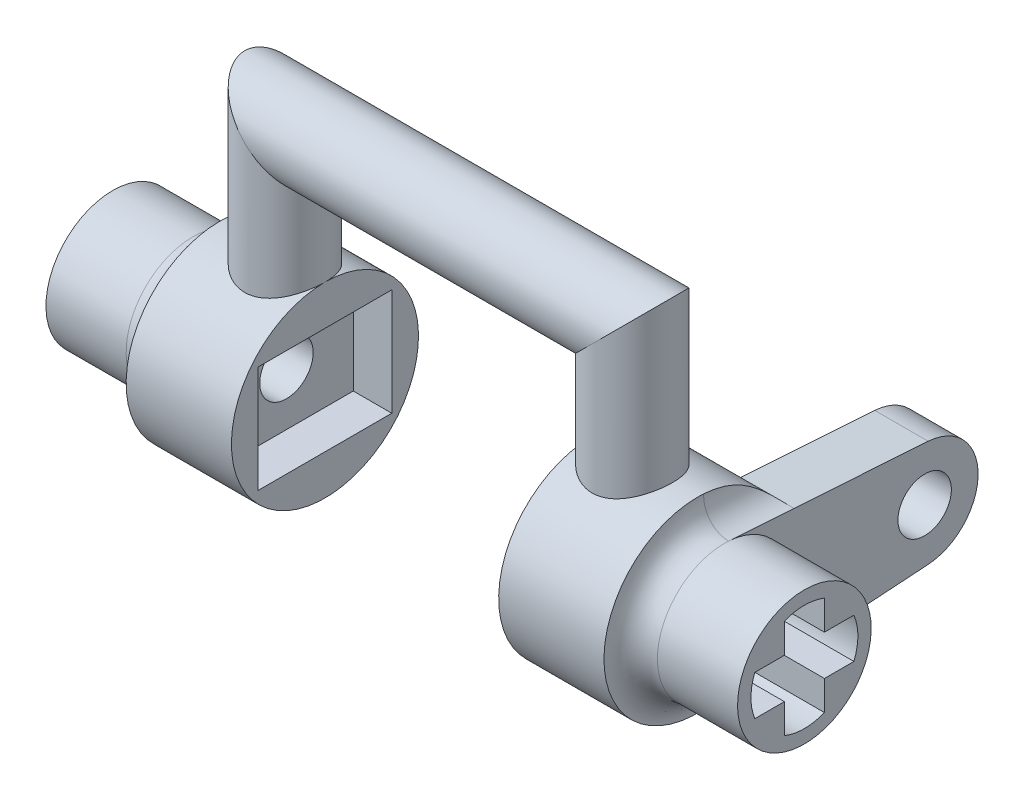
SolidWorks part; units mm, degrees
ref_plane "前视基准面" through (0, 0, 0) normal (0, 0, 1) x (1, 0, 0)
ref_plane "上视基准面" through (0, 0, 0) normal (0, 1, 0) x (1, 0, 0)
ref_plane "右视基准面" through (0, 0, 0) normal (1, 0, 0) x (0, 0, -1)
other "Configuration Table"
sketch "草图1" plane through (0, 0, 0) normal (0, 0, 1) x (1, 0, 0)
  line L0 (-210.8221, 0) -> (10330.2839, 0) construction
  line L1 (0, 0) -> (0, 8) construction
  line L2 (-6.5, 8) -> (6.5, 8)
  line L3 (6.5, 8) -> (6.5, 0)
  line L4 (6.5, 0) -> (9.5, 0)
  line L5 (-6.5, 8) -> (-6.5, 0)
  line L6 (-6.5, 0) -> (-9.5, 0)
  point P8 (0, 8)
  dimension "D1" = 8
  dimension "D2" = 13
  dimension "D3" = 3
  dimension "D4" = 3
sweep "扫描1" add path "草图1" circular profile diameter 3 parameters "D3"=3
sketch "草图8" plane through (0, 0, 0) normal (1, 0, 0) x (0, 0, -1)
  circle A0 centre (0, 0) radius 2.5
  dimension "D1" = 5
extrude "凸台-拉伸1" add sketch "草图8" along normal blind 3.44 and the other way blind 4.5 from surface starting at face at (9.5, 1.5, 0)
sketch "草图9" plane through (0, 0, 0) normal (1, 0, 0) x (0, 0, -1)
  circle A1 centre (0, 0) radius 2.5
  circle A2 centre (0, 0) radius 2.5
  dimension "D1" = 0
extrude "凸台-拉伸2" add sketch "草图9" against normal blind 3.44 and the other way blind 4.5 from surface starting at face at (-9.5, 1.5, 0)
ref_plane "基准面1" through (9.94, 0, 0) normal (1, 0, 0) x (0, 0, -1)
sketch "草图10" plane through (0, 0, 0) normal (1, 0, 0) x (0, 0, -1)
  line L0 (0.75, 0.75) -> (1.854, 0.75)
  line L1 (-1.854, 0.75) -> (-0.75, 0.75)
  line L3 (-1.854, -0.75) -> (-0.75, -0.75)
  line L5 (-1.854, 0.75) -> (1.854, -0.75) construction
  line L6 (-1.854, -0.75) -> (1.854, 0.75) construction
  line L8 (-0.75, -1.854) -> (-0.75, -0.75)
  line L10 (0.75, -1.854) -> (0.75, -0.75)
  line L11 (-0.75, -1.854) -> (0.75, 1.854) construction
  line L12 (-0.75, 1.854) -> (0.75, -1.854) construction
  line L13 (-0.75, 0.75) -> (-0.75, 1.854)
  line L14 (0.75, 0.75) -> (0.75, 1.854)
  line L16 (0.75, -0.75) -> (1.854, -0.75)
  arc A0 (-1.854, 0.75) -> (-1.854, -0.75) centre (0, 0) ccw
  arc A1 (-0.75, -1.854) -> (0.75, -1.854) centre (0, 0) ccw
  arc A2 (1.854, -0.75) -> (1.854, 0.75) centre (0, 0) ccw
  arc A3 (0.75, 1.854) -> (-0.75, 1.854) centre (0, 0) ccw
  dimension "D1" = 4
  dimension "D2" = 1.5
  dimension "D3" = 1.5
  dimension "D4" = 2.1213
  dimension "D5" = 1.104
sketch "草图14" plane through (0, 0, 0) normal (1, 0, 0) x (0, 0, -1)
  line L0 (-1000, 0) -> (49000, 0) construction
  line L1 (0.1667, 2.4944) -> (7.6333, 1.9956)
  line L2 (0.1667, -2.4944) -> (7.6333, -1.9956)
  arc A0 (7.6333, -1.9956) -> (7.6333, 1.9956) centre (7.5, 0) ccw
  circle A1 centre (0, 0) radius 2.5 construction
  circle A2 centre (7.5, 0) radius 1
  circle A3 centre (0, 0) radius 2.5
  arc A4 (0.1667, 2.4944) -> (0.1667, -2.4944) centre (0, 0) ccw
  dimension "D1" = 4
  dimension "D4" = 2
  dimension "D3" = 7.5
  dimension "D2" = 0
extrude "凸台-拉伸3" add sketch "草图14" against normal blind 2 from surface starting at plane "基准面1"
extrude "切除-拉伸1" cut sketch "草图10" against normal blind 4 from surface starting at face at (12.94, 2.5, 0)
sketch "草图11" plane through (0, 0, 0) normal (1, 0, 0) x (0, 0, -1)
  line L8 (0.75, 0.75) -> (0.75, 1.854)
  line L9 (-0.75, 1.854) -> (-0.75, 0.75)
  line L10 (-0.75, 0.75) -> (-1.854, 0.75)
  line L11 (-1.854, -0.75) -> (-0.75, -0.75)
  line L12 (-0.75, -0.75) -> (-0.75, -1.854)
  line L13 (0.75, -1.854) -> (0.75, -0.75)
  line L14 (0.75, -0.75) -> (1.854, -0.75)
  line L15 (1.854, 0.75) -> (0.75, 0.75)
  line L16 (0.75, 0.75) -> (0.75, 1.854)
  line L17 (-0.75, 1.854) -> (-0.75, 0.75)
  line L18 (-0.75, 0.75) -> (-1.854, 0.75)
  line L19 (-1.854, -0.75) -> (-0.75, -0.75)
  line L20 (-0.75, -0.75) -> (-0.75, -1.854)
  line L21 (0.75, -1.854) -> (0.75, -0.75)
  line L22 (0.75, -0.75) -> (1.854, -0.75)
  line L23 (1.854, 0.75) -> (0.75, 0.75)
  arc A4 (0.75, 1.854) -> (-0.75, 1.854) centre (0, 0) ccw
  arc A5 (-1.854, 0.75) -> (-1.854, -0.75) centre (0, 0) ccw
  arc A6 (-0.75, -1.854) -> (0.75, -1.854) centre (0, 0) ccw
  arc A7 (1.854, -0.75) -> (1.854, 0.75) centre (0, 0) ccw
  arc A8 (0.75, 1.854) -> (-0.75, 1.854) centre (0, 0) ccw
  arc A9 (-1.854, 0.75) -> (-1.854, -0.75) centre (0, 0) ccw
  arc A10 (-0.75, -1.854) -> (0.75, -1.854) centre (0, 0) ccw
  arc A11 (1.854, -0.75) -> (1.854, 0.75) centre (0, 0) ccw
  dimension "D1" = 0
extrude "切除-拉伸2" cut sketch "草图11" along normal blind 4 from surface starting at face at (-12.94, 2.5, 0)
sketch "草图16" plane through (0, 0, 0) normal (1, 0, 0) x (0, 0, -1)
  line L0 (0, 0) -> (0.75, 0) construction
  circle A0 centre (0.75, 0) radius 0.25
  dimension "D2" = 0.5
  dimension "D1" = 0.75
extrude "切除-拉伸3" cut sketch "草图16" along normal blind 0.25 from surface starting at face at (-8.94, 0, 0)
sketch "草图17" plane through (0, 0, 0) normal (1, 0, 0) x (0, 0, -1)
  circle A0 centre (0.75, 0) radius 0.25 construction
  circle A1 centre (0.75, 0) radius 0.25
extrude "切除-拉伸4" cut sketch "草图17" against normal blind 0.25 from surface starting at face at (8.94, 0, 0)
sketch "草图18" plane through (0, 0, 0) normal (1, 0, 0) x (0, 0, -1)
  circle A0 centre (0, 0) radius 3.5
  dimension "D1" = 7
extrude "凸台-拉伸4" add sketch "草图18" along normal up to surface (8.94 mm away) from surface up to face at (8.94, 0.25, -0.75) starting at face at (5, 2.5, 0)
sketch "草图20" plane through (0, 0, 0) normal (1, 0, 0) x (0, 0, -1)
  circle A0 centre (0, 0) radius 3.5
  dimension "D1" = 7
extrude "凸台-拉伸5" add sketch "草图20" along normal up to surface (-5 mm away) from surface up to face at (-5, 2.5, 0) starting at face at (-8.94, 0.25, -0.75)
sketch "草图22" plane through (0, 0, 0) normal (0, 1, 0) x (1, 0, 0)
  line L0 (-8.94, 2.5) -> (-8.94, -2.5) construction
  line L1 (-8.94, 2.5) -> (-8.94, -2.5) construction
  line L2 (-8.94, 0) -> (-6.44, 0) construction
  line L3 (-8.94, 0) -> (-12.94, 0) construction
  line L4 (-6.44, -2.5) -> (-6.44, 2.5)
  line L5 (-6.44, -2.5) -> (-5, -2.5)
  line L6 (-5, -3.5) -> (-5, 3.5) construction
  line L7 (-5, -2.5) -> (-5, 2.5)
  line L8 (-5, 2.5) -> (-6.44, 2.5)
  line L9 (0, -1000) -> (0, 49000) construction
  line L10 (5, 2.5) -> (6.44, 2.5)
  line L11 (6.44, -2.5) -> (6.44, 2.5)
  line L12 (6.44, -2.5) -> (5, -2.5)
  line L13 (5, -2.5) -> (5, 2.5)
  point P10 (-6.44, 0)
  dimension "D1" = 2.5
  dimension "D2" = 5
extrude "切除-拉伸5" cut sketch "草图22" against normal blind 2 and the other way blind 2
sketch "草图25" plane through (0, 0, 0) normal (1, 0, 0) x (0, 0, -1)
  circle A0 centre (0, 0) radius 1
  dimension "D1" = 2
extrude "切除-拉伸6" cut sketch "草图25" against normal through all and the other way through all
fillet "圆角1" radius 1 4 edges at (-8.94, 2.5, 0) (8.94, 0, 2.5) (8.94, -2.4128, -1.3887) (8.94, 2.4128, -1.3887) first distance on face at (-12.94, 2.5, 0) first distance on face at (8.94, 0, 0.8057)
